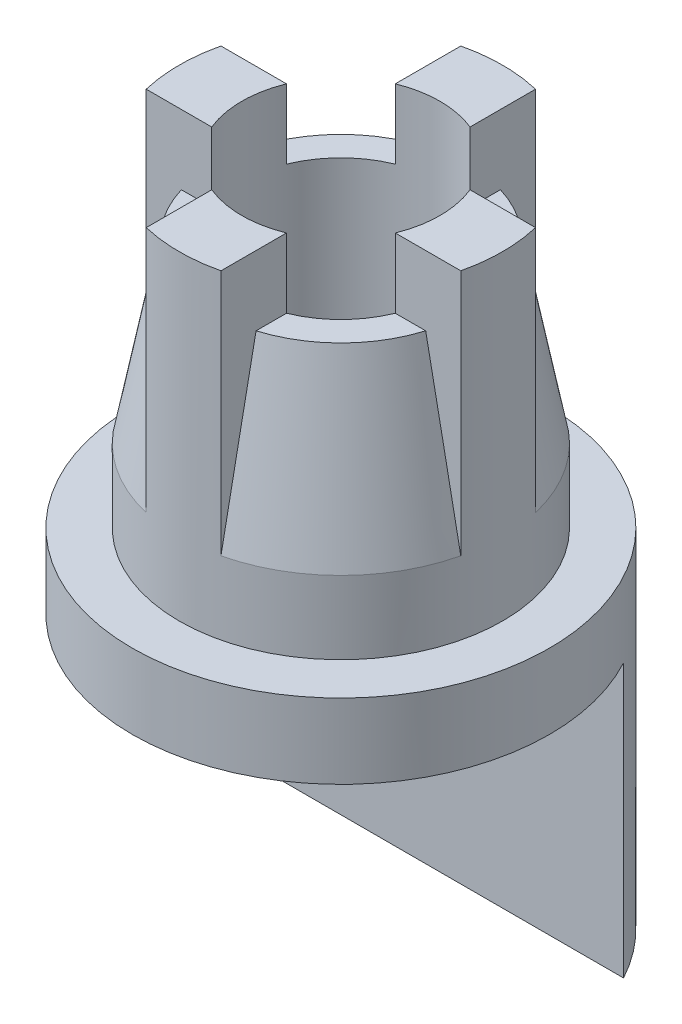
SolidWorks part; units mm, degrees
ref_plane "Front Plane" through (0, 0, 0) normal (0, 0, 1) x (1, 0, 0)
ref_plane "Top Plane" through (0, 0, 0) normal (0, 1, 0) x (1, 0, 0)
ref_plane "Right Plane" through (0, 0, 0) normal (1, 0, 0) x (0, 0, -1)
sketch "Croquis1" plane through (0, 0, 0) normal (0, 1, 0) x (1, 0, 0)
  circle A0 centre (0, 0) radius 6
  dimension "D1" = 12
extrude "Saliente-Extruir1" add sketch "Croquis1" along normal blind 2.15
sketch "Croquis4" plane through (0, 2.15, 0) normal (0, 1, 0) x (1, 0, 0)
  circle A0 centre (0, 0) radius 4.65
  dimension "D1" = 9.3
extrude "Saliente-Extruir3" add sketch "Croquis4" along normal blind 7.2
sketch "Croquis2" plane through (0, 2.15, 0) normal (0, 1, 0) x (1, 0, 0)
  circle A0 centre (0, 0) radius 2.85
  dimension "D1" = 5.7
extrude "Cortar-Extruir1" cut sketch "Croquis2" against normal through all and the other way blind 7.2
sketch "Croquis3" plane through (0, 2.15, 0) normal (0, 1, 0) x (1, 0, 0)
  line L0 (-5.2799, 2.85) -> (5.2799, 2.85)
  line L1 (0, 0) -> (0, 5.6987) construction
  circle A0 centre (0, 0) radius 6 construction
  circle A1 centre (0, 0) radius 2.85 construction
  arc A2 (5.2799, 2.85) -> (-5.2799, 2.85) centre (0, 0) ccw
extrude "Saliente-Extruir2" add sketch "Croquis3" against normal blind 10
chamfer "Chaflán1" distance 5.1 distance2 0.975 1 edges at (0, 9.35, 4.65) first distance on face at (0, 9.35, 4.65)
sketch "Croquis6" plane through (0, 2.15, 0) normal (0, 1, 0) x (1, 0, 0)
  line L0 (-4.65, 0) -> (4.65, 0) construction
  line L1 (0, -4.65) -> (0, 4.65) construction
  line L2 (-4.524, -1.075) -> (-2.6395, -1.075)
  line L3 (-4.524, 1.075) -> (-2.6395, 1.075)
  line L4 (1.075, -4.524) -> (1.075, -2.6395)
  line L5 (-1.075, -4.524) -> (-1.075, -2.6395)
  line L6 (-1.075, -6.5742) -> (-1.075, 6.1285) construction
  line L7 (0, -6.5742) -> (0, 6.1285) construction
  line L8 (1.075, -6.5742) -> (1.075, 6.1285) construction
  line L9 (-6.4787, -1.075) -> (8.166, -1.075) construction
  line L10 (-6.4787, 0) -> (8.166, 0) construction
  line L11 (-6.4787, 1.075) -> (8.166, 1.075) construction
  line L12 (2.6395, 1.075) -> (4.524, 1.075)
  line L13 (-1.075, 2.6395) -> (-1.075, 4.524)
  line L14 (1.075, 2.6395) -> (1.075, 4.524)
  line L15 (2.6395, -1.075) -> (4.524, -1.075)
  circle A0 centre (0, 0) radius 2.85 construction
  circle A1 centre (0, 0) radius 4.65 construction
  arc A3 (2.6395, -1.075) -> (2.6395, 1.075) centre (0, 0) ccw
  arc A4 (4.524, -1.075) -> (4.524, 1.075) centre (0, 0) ccw
  arc A5 (1.075, 4.524) -> (-1.075, 4.524) centre (0, 0) ccw
  arc A6 (1.075, 2.6395) -> (-1.075, 2.6395) centre (0, 0) ccw
  arc A7 (-2.6395, 1.075) -> (-2.6395, -1.075) centre (0, 0) ccw
  arc A8 (-4.524, 1.075) -> (-4.524, -1.075) centre (0, 0) ccw
  arc A9 (-1.075, -4.524) -> (1.075, -4.524) centre (0, 0) ccw
  arc A10 (-1.075, -2.6395) -> (1.075, -2.6395) centre (0, 0) ccw
  dimension "D1" = 1.075
  dimension "D2" = 1.075
  dimension "D3" = 1.075
  dimension "D4" = 1.075
extrude "Saliente-Extruir4" add sketch "Croquis6" along normal blind 9.2
